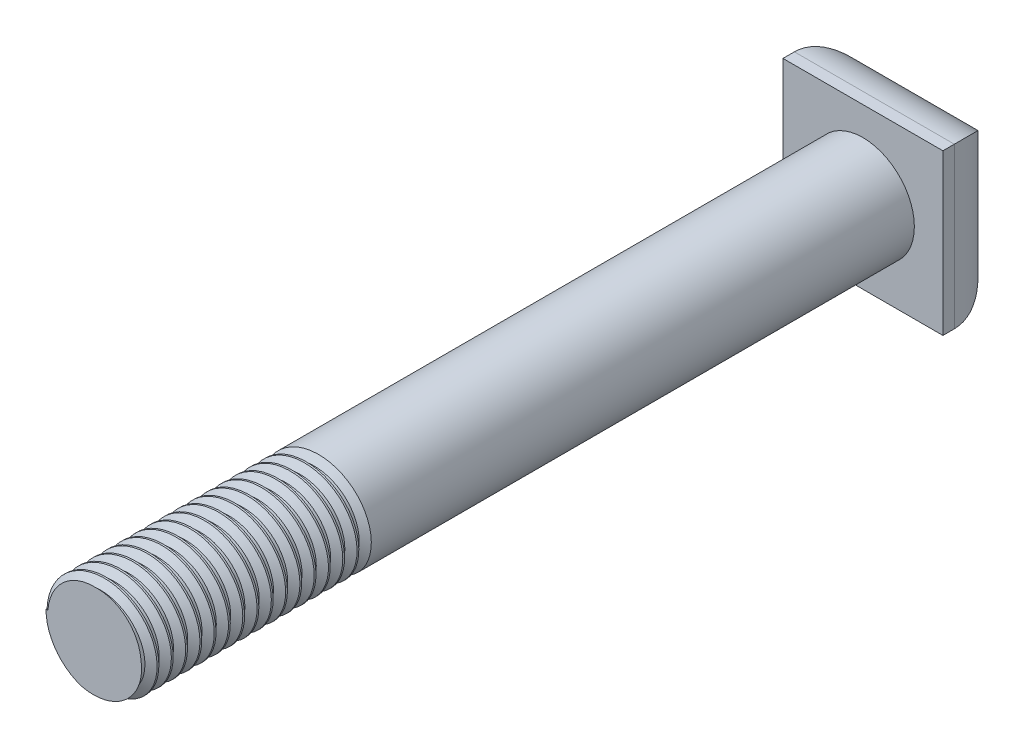
SolidWorks part; units mm, degrees
ref_plane "Front Plane" through (0, 0, 0) normal (0, 0, 1) x (1, 0, 0)
ref_plane "Top Plane" through (0, 0, 0) normal (0, 1, 0) x (1, 0, 0)
ref_plane "Right Plane" through (0, 0, 0) normal (1, 0, 0) x (0, 0, -1)
sketch "Sketch1" plane through (0, 0, 0) normal (0, 0, 1) x (1, 0, 0)
  line L1 (14, -14) -> (-14, -14)
  line L2 (14, -14) -> (14, 14)
  line L3 (14, 14) -> (-14, 14)
  line L4 (-14, -14) -> (-14, 14)
  line L5 (14, -14) -> (-14, 14) construction
  line L6 (14, 14) -> (-14, -14) construction
  point P0 (0, 0)
  dimension "D1" = 28
extrude "Boss-Extrude1" add sketch "Sketch1" along normal blind 12
sketch "Sketch2" plane through (0, 0, 12) normal (0, 0, 1) x (1, 0, 0)
  circle A0 centre (0, 0) radius 9
  dimension "D1" = 18
extrude "Boss-Extrude2" add sketch "Sketch2" along normal blind 134
thread "Thread1" pitch 2.5 method cut trim with start face yes profile "Thread Profile1" start angle 0, offset 2, length 40, pitch 2.5, diameter 18
ref_plane "Plane1" through (-9, 0, 148) normal (0, -1, 0) x (-1, 0, 0)
sketch "Thread Profile1" plane through (-9, 0, 148) normal (0, -1, 0) x (-1, 0, 0)
  line L0 (0, 0) -> (0, 2.5) construction
  line L11 (0, 0) -> (0, 2.1875)
  line L12 (0, 2.1875) -> (-1.3532, 1.4062)
  line L13 (-1.3532, 1.4062) -> (-1.3532, 0.7812)
  line L15 (-1.3532, 0.7812) -> (0, 0)
  line L17 (-1.3532, 1.0937) -> (0, 1.0937) construction
  point P2 (0, 0)
  dimension "Pitch" = 2.5
  dimension "Profile_Angle" = 60
  dimension "Profile_Land" = 0.625
  dimension "Profile_Height" = 1.3532
fillet "Fillet1" radius 10 4 edges at (0, -14, 0) (14, 0, 0) (0, 14, 0) (-14, 0, 0)
